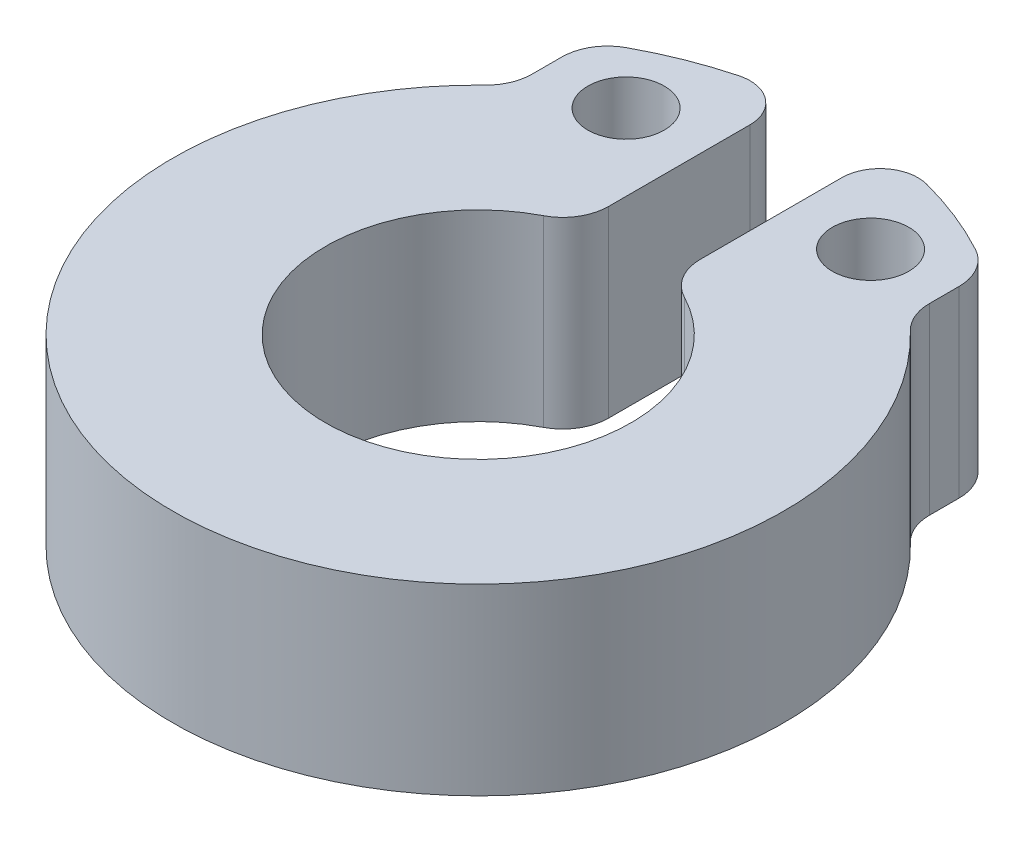
SolidWorks part; units mm, degrees
ref_plane "Front Plane" through (0, 0, 0) normal (0, 0, 1) x (1, 0, 0)
ref_plane "Top Plane" through (0, 0, 0) normal (0, 1, 0) x (1, 0, 0)
ref_plane "Right Plane" through (0, 0, 0) normal (1, 0, 0) x (0, 0, -1)
sketch "Sketch1" plane through (0, 0, 0) normal (0, 1, 0) x (1, 0, 0)
  line L0 (-0.3, 0.9539) -> (-0.3, 2.3812)
  line L1 (0.3, 0.9539) -> (0.3, 2.3812)
  line L2 (-1.3, 1.5199) -> (-1.3, 2.0174)
  line L3 (1.3, 1.5199) -> (1.3, 2.0174)
  line L4 (-1.3, 2.0174) -> (-0.3, 2.0174) construction
  line L5 (1.3, 2.0174) -> (0.3, 2.0174) construction
  arc A0 (-0.3, 0.9539) -> (0.3, 0.9539) centre (0, 0) ccw
  arc A1 (-1.3, 1.5199) -> (1.3, 1.5199) centre (0, 0) ccw
  arc A2 (1.3, 2.0174) -> (0.3, 2.3812) centre (0, 0) ccw
  circle A3 centre (0, 0) radius 2.4 construction
  arc A4 (-0.3, 2.3812) -> (-1.3, 2.0174) centre (0, 0) ccw
  circle A5 centre (0, 0) radius 2 construction
  circle A6 centre (0, 0) radius 1 construction
  circle A7 centre (-0.8, 1.7674) radius 0.25
  circle A8 centre (0.8, 1.7674) radius 0.25
  point P1 (-0.8, 2.0174)
  point P22 (0, 0)
  point P24 (0.8, 2.0174)
  dimension "D1" = 2
  dimension "D6" = 0.5
  dimension "D3" = 0.6
  dimension "D4" = 0.4
  dimension "D5" = 1
  dimension "D7" = 0.25
  dimension "D2" = 1
extrude "Boss-Extrude1" add sketch "Sketch1" along normal blind 1.2
fillet "Fillet1" radius 0.3 6 edges at (-1.3, 0.6, -2.0174) (1.3, 0.6, -2.0174) (1.3, 0.6, -1.5199) (-1.3, 0.6, -1.5199) (0.3, 0.6, -0.9539) (-0.3, 0.6, -0.9539)
fillet "Fillet2" radius 0.25 2 edges at (0.3, 0.6, -2.3812) (-0.3, 0.6, -2.3812)
